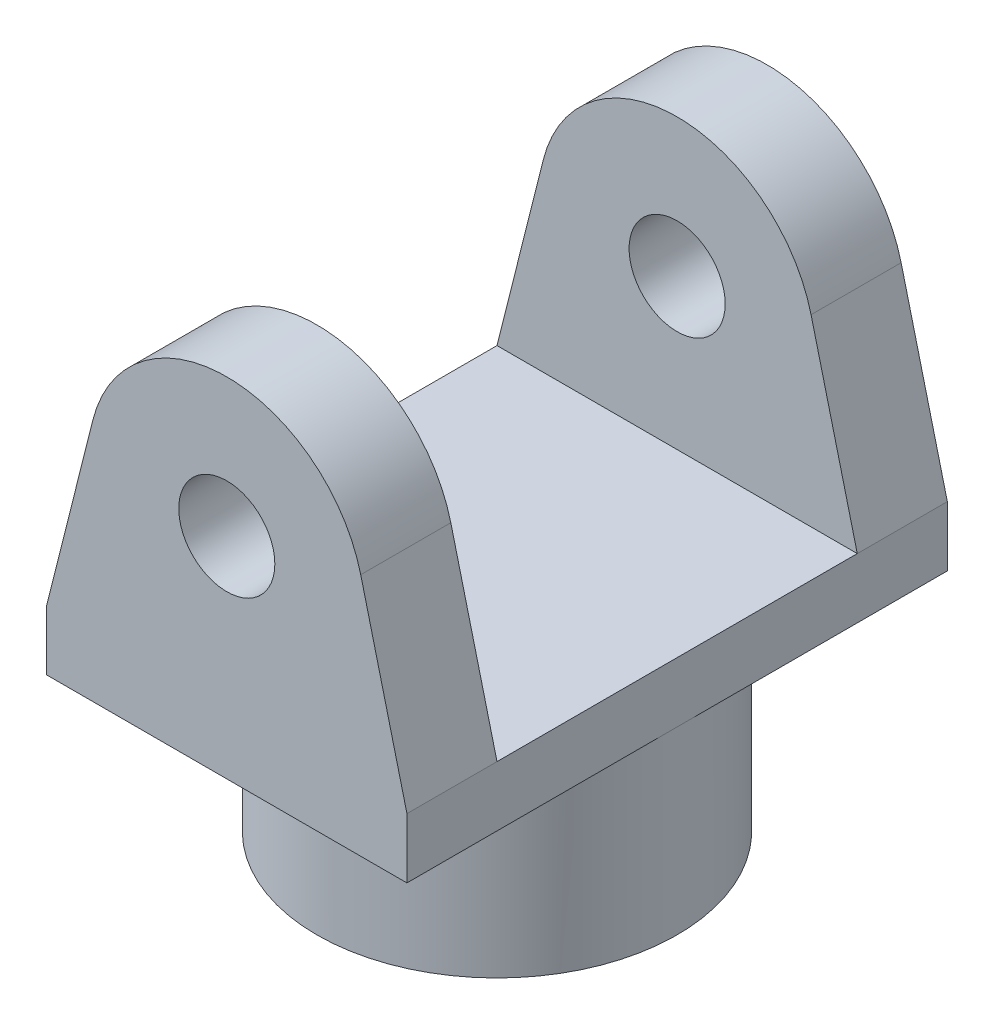
SolidWorks part; units mm, degrees
ref_plane "Front Plane" through (0, 0, 0) normal (0, 0, 1) x (1, 0, 0)
ref_plane "Top Plane" through (0, 0, 0) normal (0, 1, 0) x (1, 0, 0)
ref_plane "Right Plane" through (0, 0, 0) normal (1, 0, 0) x (0, 0, -1)
sketch "Sketch1" plane through (0, 0, 0) normal (0, 1, 0) x (1, 0, 0)
  line L0 (0, -45) -> (0, 45) construction
  line L1 (30, -45) -> (-30, -45)
  line L2 (30, -45) -> (30, 45)
  line L3 (30, 45) -> (-30, 45)
  line L4 (-30, -45) -> (-30, 45)
  line L5 (30, -45) -> (-30, 45) construction
  line L6 (30, 45) -> (-30, -45) construction
  line L7 (-30, 0) -> (30, 0) construction
  line L8 (5, 14.1421) -> (5, 20.1421)
  line L9 (-5, 14.1421) -> (-5, 20.1421)
  line L10 (-5, 20.1421) -> (5, 20.1421)
  circle A0 centre (0, 0) radius 30
  circle A1 centre (0, 0) radius 15
  point P0 (0, 0)
  point P13 (0, 0)
  point P16 (0, 0)
  point P17 (5, 5.5902)
  dimension "D1" = 60
  dimension "D2" = 30
  dimension "D3" = 10
  dimension "D4" = 6
  dimension "D5" = 90
extrude "Boss-Extrude1" add sketch "Sketch1" along normal blind 10 contours A0 L4 L1 | A0 A1 L9 L10 L8 | A0 L3 L4 | A0 L2 L3 | A0 L1 L2 | A1 | A1 L8 L10 L9 region at (0, 0, 33.2353) region at (0, 0, -33.2353) region at (0, 0, 29.1515) region at (0, 0, -17.4238) region at (0, 0, 0)
extrude "Boss-Extrude2" add sketch "Sketch1<3>" against normal blind 30 contours A0 A1 L9 L10 L8 region at (0, 0, 29.1515)
sketch "Sketch1<3>" plane through (0, 0, 0) normal (0, 1, 0) x (1, 0, 0) same geometry as "Sketch1"
sketch "Sketch3" plane through (0, 0, 45) normal (0, 0, 1) x (1, 0, 0)
  line L0 (0, 0) -> (0, 66.5572) construction
  line L1 (-29.2608, 35) -> (29.2608, 35) construction
  line L2 (30, 0) -> (-30, 0) construction
  line L3 (-30, 10) -> (-22.306, 40.6072)
  line L4 (30, 10) -> (22.306, 40.6072)
  circle A0 centre (0, 35) radius 8
  arc A1 (22.306, 40.6072) -> (-22.306, 40.6072) centre (0, 35) ccw
  point P6 (0, 35)
  line M8 (30, 10) -> (-30, 10)
  dimension "D2" = 16
  dimension "D3" = 46
  dimension "D1" = 35
extrude "Boss-Extrude3" add sketch "Sketch3" against normal blind 15 contours L4 A1 L3 A0 M8 region at (-25.4078, 25.1163, 45)
ref_plane "Plane1" through (0, 0, 0) normal (0, 0, 1) x (1, 0, 0)
mirror "Mirror1" about plane through (0, 0, 0) normal (0, 0, 1) of "Boss-Extrude3"
